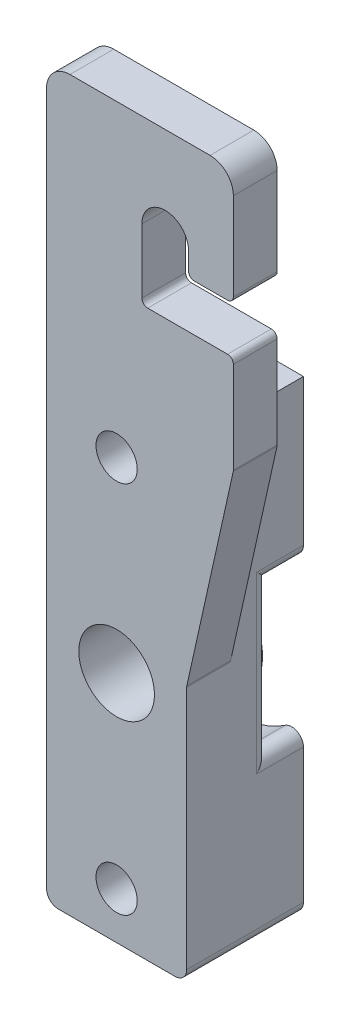
SolidWorks part; units mm, degrees
material "ABS"
ref_plane "Front" through (0, 0, 0) normal (0, 0, 1) x (1, 0, 0)
ref_plane "Top" through (0, 0, 0) normal (0, 1, 0) x (1, 0, 0)
ref_plane "Right" through (0, 0, 0) normal (1, 0, 0) x (0, 0, -1)
sketch "Sketch1" plane through (0, 0, 0) normal (0, 0, 1) x (1, 0, 0)
  line L1 (-9.525, 31.75) -> (9.525, 31.75)
  line L2 (-9.525, 31.75) -> (-9.525, -31.75)
  line L3 (-9.525, -31.75) -> (9.525, -31.75)
  line L4 (9.525, 31.75) -> (9.525, -31.75)
  line L5 (-9.525, 31.75) -> (9.525, -31.75) construction
  line L6 (-9.525, -31.75) -> (9.525, 31.75) construction
  point P0 (0, 0)
  dimension "D1" = 19.05
  dimension "D2" = 63.5
extrude "Boss-Extrude1" add sketch "Sketch1" along normal blind 15.875
sketch "Sketch2" plane through (0, 0, 15.875) normal (0, 0, 1) x (1, 0, 0)
  line L0 (0, 31.75) -> (0, -31.75) construction
  line L1 (9.525, 31.75) -> (-9.525, 31.75) construction
  line L2 (-9.525, -31.75) -> (9.525, -31.75) construction
  circle A0 centre (0, 0) radius 5.1435
  dimension "D1" = 10.287
extrude "Cut-Extrude1" cut sketch "Sketch2" against normal through all
sketch "Sketch3" plane through (0, 0, 15.875) normal (0, 0, 1) x (1, 0, 0)
  circle A0 centre (0, 0) radius 12.7
  dimension "D1" = 25.4
extrude "Cut-Extrude2" cut sketch "Sketch3" against normal blind 3.9688
sketch "Sketch4" plane through (0, 0, 11.9062) normal (0, 0, 1) x (1, 0, 0)
  circle A0 centre (0, 0) radius 12.7
  circle A1 centre (0, 0) radius 7.9375
  dimension "D1" = 15.875
extrude "Cut-Extrude3" cut sketch "Sketch4" against normal blind 0.7937
hole_wizard "#10 Clearance Hole1" positions "Sketch5" profile "Sketch6" hole size "#10" standard "ANSI Inch"
sketch "Sketch5" plane through (0, 0, 15.875) normal (0, 0, 1) x (1, 0, 0)
  line L0 (0, 31.75) -> (0, -31.75) construction
  line L1 (9.525, 31.75) -> (-9.525, 31.75) construction
  line L2 (-9.525, -31.75) -> (9.525, -31.75) construction
  point P9 (0, -25.4)
  point P11 (0, 25.4)
  dimension "D1" = 25.4
  dimension "D2" = 25.4
sketch "Sketch6" plane through (0, 25.4, 15.875) normal (1, 0, 0) x (0, -1, 0)
  line L0 (0, 0) -> (0, 27.0864)
  line L1 (0, 27.0864) -> (2.8067, 25.4)
  line L2 (2.8067, 25.4) -> (2.8067, 0)
  line L5 (2.8067, 0) -> (0, 0)
  line L10 (0, 27.0864) -> (-2.8067, 25.4) construction
  line L11 (0, -6.35) -> (0, 107.95) construction
  dimension "Hole Dia." = 5.6134
  dimension "Hole Depth" = 25.4
  dimension "Drill Angle" = 118
fillet "Fillet1" radius 1.5875 8 edges at (-9.525, -31.75, 7.9375) (9.525, -31.75, 7.9375) (-9.525, 8.4003, 13.4938) (-9.525, -8.4003, 13.4938) (9.525, -8.4003, 13.4938) (9.525, 8.4003, 13.4938) (9.525, 0, 11.1125) (-9.525, 0, 11.1125)
sketch "Sketch7" [suppressed] plane through (0, 0, 15.875) normal (0, 0, 1) x (1, 0, 0)
  line L0 (0, 0) -> (-1.5875, 0) construction
  line L1 (0, -5.08) -> (-1.5875, -5.08)
  line L2 (0, 5.08) -> (-1.5875, 5.08)
  arc A0 (0, -5.08) -> (0, 5.08) centre (0, 0) ccw
  arc A1 (-1.5875, 5.08) -> (-1.5875, -5.08) centre (-1.5875, 0) ccw
  point P3 (-0.7937, 0)
  dimension "D1" = 5.08
  dimension "D2" = 1.5875
extrude "Cut-Extrude4" [suppressed] cut sketch "Sketch7" against normal through all
sketch "Sketch8" [suppressed] plane through (0, 0, 15.875) normal (0, 0, 1) x (1, 0, 0)
  line L0 (0, 0) -> (-1.5875, 0) construction
  line L1 (0, -12.7) -> (-1.5875, -12.7)
  line L2 (0, 12.7) -> (-1.5875, 12.7)
  arc A0 (0, -12.7) -> (0, 12.7) centre (0, 0) ccw
  arc A1 (-1.5875, 12.7) -> (-1.5875, -12.7) centre (-1.5875, 0) ccw
  point P4 (-0.7937, 0)
  dimension "D1" = 12.7
extrude "Cut-Extrude5" [suppressed] cut sketch "Sketch8" against normal blind 3.9688
sketch "Sketch9" [suppressed] plane through (0, 0, 11.9062) normal (0, 0, 1) x (1, 0, 0)
  line L0 (0, 0) -> (-1.5875, 0) construction
  line L1 (0, -12.7) -> (-1.5875, -12.7)
  line L2 (0, 12.7) -> (-1.5875, 12.7)
  line L3 (0, 0) -> (-1.5875, 0) construction
  line L4 (0, -6.2706) -> (-1.5875, -6.2706)
  line L5 (0, 6.2706) -> (-1.5875, 6.2706)
  arc A0 (0, -12.7) -> (0, 12.7) centre (0, 0) ccw
  arc A1 (-1.5875, 12.7) -> (-1.5875, -12.7) centre (-1.5875, 0) ccw
  arc A2 (0, -6.2706) -> (0, 6.2706) centre (0, 0) ccw
  arc A3 (-1.5875, 6.2706) -> (-1.5875, -6.2706) centre (-1.5875, 0) ccw
  arc A4 (-1.5875, 5.08) -> (-1.5875, -5.08) centre (-1.5875, 0) ccw construction
  point P4 (-0.7937, 0)
  point P9 (-0.7937, 0)
  dimension "D1" = 1.1906
extrude "Cut-Extrude6" [suppressed] cut sketch "Sketch9" against normal blind 0.7937
sketch "Sketch12" plane through (0, 0, 0) normal (0, 0, -1) x (-1, 0, 0)
  line L0 (-15.875, 51.435) -> (-15.875, 67.31)
  line L1 (9.525, 31.75) -> (-15.875, 31.75)
  line L2 (9.525, 31.75) -> (9.525, 67.31)
  line L3 (9.525, 67.31) -> (-15.875, 67.31)
  line L4 (-15.875, 31.75) -> (-15.875, 45.085)
  line L9 (-9.525, -30.1625) -> (-9.525, 31.75) construction
  line L10 (-15.875, 51.435) -> (-9.779, 51.435)
  line L11 (-15.875, 45.085) -> (-3.429, 45.085)
  line L12 (-15.875, 31.75) -> (-9.525, 3.175)
  line L14 (-9.779, 54.61) -> (-9.779, 51.435)
  line L15 (-3.429, 45.085) -> (-3.429, 54.61)
  line L16 (-9.525, 31.75) -> (9.525, 31.75) construction
  line L17 (9.525, 31.75) -> (9.525, -30.1625) construction
  arc A0 (-3.429, 54.61) -> (-9.779, 54.61) centre (-6.604, 54.61) ccw
  dimension "D1" = 6.35
  dimension "D3" = 16.129
  dimension "D2" = 6.35
  dimension "D4" = 13.335
  dimension "D5" = 3.175
  dimension "D6" = 25.4
  dimension "D7" = 12.7
  dimension "D8" = 28.575
extrude "Boss-Extrude2" add sketch "Sketch12" against normal offset from surface (5.9531 mm away) 9.9219 up to face at (2.8067, 25.4, 15.875)
fillet "Fillet2" [suppressed] radius 1.5875
hole_wizard "Tap Drill for #6-32 Tap1" [suppressed] positions "Sketch10" profile "Sketch11" hole size "#6-32" standard "ANSI Inch"
sketch "Sketch10" plane through (9.525, 0, 0) normal (1, 0, 0) x (0, 0, -1)
  line L0 (-9.525, 0) -> (0, 0) construction
  line L1 (-9.525, 11.8798) -> (-9.525, -11.8798) construction
  point P7 (-4.7625, 0)
sketch "Sketch11" plane through (9.525, 0, 4.7625) normal (0, 1, 0) x (0, 0, -1)
  line L0 (0, 0) -> (0, 4.445)
  line L1 (0, 4.445) -> (1.3525, 4.445)
  line L2 (1.3525, 4.445) -> (1.3525, 0)
  line L5 (1.3525, 0) -> (0, 0)
  line L11 (0, -6.35) -> (0, 107.95) construction
  dimension "Thru Hole Dia." = 2.7051
  dimension "Thru Hole Depth" = 4.445
fillet "Fillet3" radius 0.7937 6 edges at (3.429, 45.085, 2.9766) (9.779, 51.435, 2.9766) (15.875, 51.435, 2.9766) (15.875, 45.085, 2.9766) (15.875, 31.75, 2.9766) (9.525, 3.175, 2.9766)
fillet "Fillet4" radius 3.175 2 edges at (-9.525, 67.31, 2.9766) (15.875, 67.31, 2.9766)
mirror "Mirror1" about plane through (0, 0, 15.875) normal (0, 0, 1) of bodies 110
delete or keep bodies "Body-Delete/Keep 1" type delete bodies bodies 110
equation "\"D1@Boss-Extrude2\"=.75/2 +1/64"
